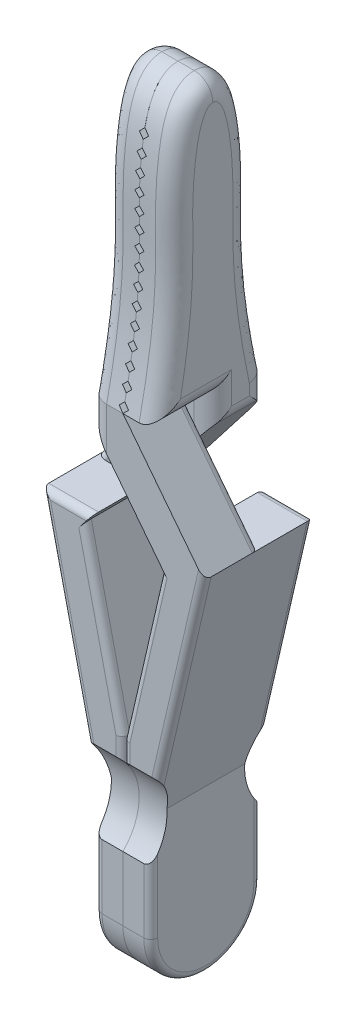
SolidWorks part; units mm, degrees
material "AISI 316 Stainless Steel Sheet (SS)"
ref_plane "Front Plane" through (0, 0, 0) normal (0, 0, 1) x (1, 0, 0)
ref_plane "Top Plane" through (0, 0, 0) normal (0, 1, 0) x (1, 0, 0)
ref_plane "Right Plane" through (0, 0, 0) normal (1, 0, 0) x (0, 0, -1)
sketch "Sketch5" plane through (0, 0, 0) normal (0, 0, 1) x (1, 0, 0)
  line L0 (0, 12.8404) -> (0, 0)
  line L2 (0, 0) -> (3.1622, -4.0657)
  line L3 (3.1622, -4.0657) -> (1.5, -11.2927)
  line L4 (0, 12.8404) -> (1.5, 12.8404)
  line L5 (1.5, 12.8404) -> (1.5, 0.8404)
  line L6 (1.5, 0.8404) -> (5, -3.6596)
  line L7 (5, -3.6596) -> (2.7, -13.6596)
  line L8 (2.7, -13.6596) -> (2.7, -20.6596)
  line L9 (2.7, -20.6596) -> (1.5, -20.6596)
  line L10 (1.5, -20.6596) -> (1.5, -11.2927)
  dimension "D1" = 1.7
  dimension "D2" = 1.5
  dimension "D3" = 12
  dimension "D4" = 10
  dimension "D5" = 7
  dimension "D6" = 1.2
  dimension "D7" = 1.7
  dimension "D8" = 4.5
  dimension "D9" = 5
extrude "Boss-Extrude2" add sketch "Sketch5" along normal blind 4.75
sketch "Sketch6" plane through (0, 0, 0) normal (1, 0, 0) x (0, 0, -1)
  line L0 (0, -3.6596) -> (-2.375, -3.6596)
  line L1 (-2.375, -3.6596) -> (-2.375, 0.8404)
  line L2 (-2.375, 0.8404) -> (0, 0.8404)
  line L3 (-4.75, -3.6596) -> (0, -3.6596) construction
  line L4 (-4.75, 0.8404) -> (0, 0.8404) construction
  line L5 (0, -11.2927) -> (0, -20.6596) construction
  line L6 (0, -15.5113) -> (0, -20.6596) construction
  line L7 (0, 0.8404) -> (0, 12.8404) construction
  line L8 (-2.375, 0.8404) -> (-4.75, 0.8404) construction
  line L9 (-4.75, 0.8404) -> (-4.75, 12.8404) construction
  line L10 (0, -20.6596) -> (-2.375, -20.6596) construction
  line L11 (-4.75, -20.6596) -> (0, -20.6596) construction
  line L12 (0, -18.2846) -> (0, -15.5113)
  line L13 (0, -12.1206) -> (0, -3.6596)
  line L14 (-2.375, 12.8116) -> (-2.375, 7.4216) construction
  line L15 (-4.75, -18.2846) -> (-4.75, -15.5113)
  line L16 (-4.75, 0.8404) -> (-4.75, -12.1206)
  line L17 (-4.75, -11.2927) -> (-4.75, -20.6596) construction
  arc A0 (0, -12.1206) -> (0, -15.5113) centre (1.6954, -13.8159) ccw
  arc A1 (-2.375, -20.6596) -> (0, -18.2846) centre (-2.375, -18.2846) ccw
  arc A2 (-2.375, -20.6596) -> (-4.75, -18.2846) centre (-2.375, -18.2846) cw
  arc A3 (-4.75, -12.1206) -> (-4.75, -15.5113) centre (-6.4454, -13.8159) cw
  spline S0 degree 3 poles (0, 0.8404) (-1.1598, 6.2352) (-0.1869, 8.0351) (-1.2912, 12.7915) (-2.375, 12.8116) knots 0 0 0 0 0.723762 1 1 1 1
  spline S1 degree 3 poles (-4.75, 0.8404) (-3.5902, 6.2352) (-4.5631, 8.0351) (-3.4588, 12.7915) (-2.375, 12.8116) knots 0 0 0 0 0.723762 1 1 1 1
extrude "Cut-Extrude7" cut sketch "Sketch6" along normal through all and the other way through all flip side to cut
ref_plane "Plane2" through (0, 0, 2.375) normal (0, 0, 1) x (1, 0, 0)
fillet "Fillet2" radius 0.8 6 edges at (0, 0.4202, 2.375) (0, 0, 3.5625)
sketch "Sketch8" plane through (0, 0, 2.375) normal (0, 0, 1) x (1, 0, 0)
  line L0 (1.5, 1.2404) -> (1.3, 1.0404)
  line L1 (1.3, 1.0404) -> (1.5, 0.8404)
  line L2 (1.5, 0.8404) -> (1.5, 1.2404)
  line L3 (1.5, 0.8404) -> (1.5, 12.8116) construction
  dimension "D1" = 0.4
extrude "Cut-Extrude8" cut sketch "Sketch8" against normal through all and the other way through all
pattern_linear "LPattern2" count 15 spacing 0.7 along (0, 1, 0) of "Cut-Extrude8"
fillet "Fillet4" radius 0.3 11 edges at (3.25, -1.4096, 2.375) (3.9232, -3.6596, 0) (4.027, -7.8901, 0) (1.5, -11.7066, 4.75) (1.5, -11.7066, 0) (2.3311, -7.6792, 4.75) (2.3311, -7.6792, 0) (2.7, -16.8979, 4.75) (2.7, -16.8979, 0) (4.027, -7.8901, 4.75) (2.7, -20.6596, 2.375)
ref_axis "Axis2" through (1.5, 14.4852, 2.375) along (0, -1, 0)
pattern_circular "CirPattern2" count 2 over 360 about axis through (1.5, 14.4852, 2.375) along (0, -1, 0) of bodies 112
